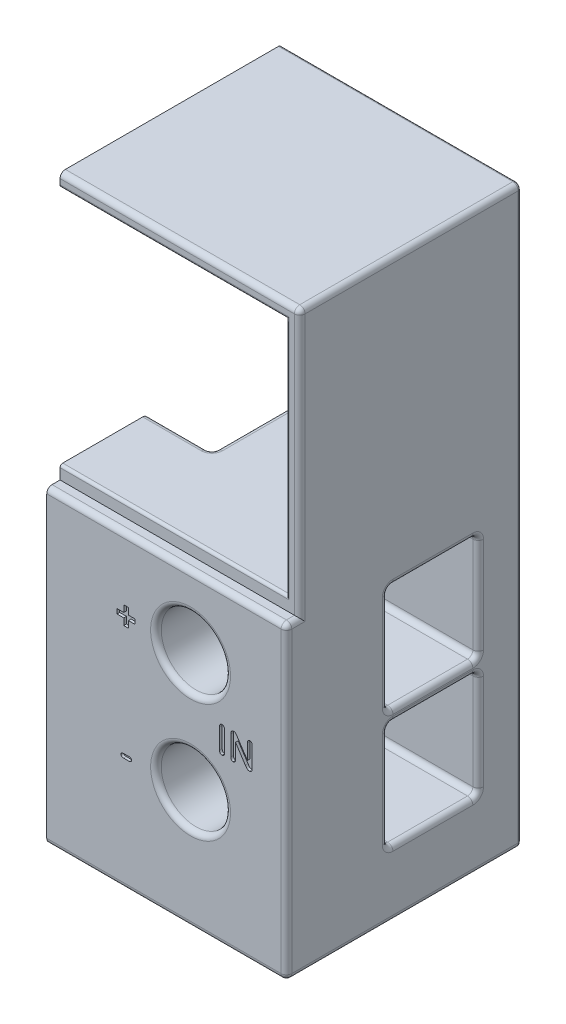
SolidWorks part; units mm, degrees
ref_plane "Front Plane" through (0, 0, 0) normal (0, 0, 1) x (1, 0, 0)
ref_plane "Top Plane" through (0, 0, 0) normal (0, 1, 0) x (1, 0, 0)
ref_plane "Right Plane" through (0, 0, 0) normal (1, 0, 0) x (0, 0, -1)
sketch "Sketch2" plane through (0, 0, 0) normal (0, 0, 1) x (1, 0, 0)
  line L0 (0, 32.5) -> (0, 0) construction
  line L1 (43.9999, -54) -> (-43.9999, -54)
  line L2 (43.9999, -54) -> (43.9999, 54)
  line L3 (43.9999, 54) -> (-43.9999, 54)
  line L4 (-43.9999, -54) -> (-43.9999, 54)
  line L5 (43.9999, -54) -> (-43.9999, 54) construction
  line L6 (43.9999, 54) -> (-43.9999, -54) construction
  line L9 (0, 0) -> (0, -20.5) construction
  line L10 (-31.75, 43.125) -> (31.75, 43.125)
  line L11 (-31.75, 43.125) -> (-31.75, 21.875)
  line L12 (-31.75, 21.875) -> (31.75, 21.875)
  line L13 (31.75, 43.125) -> (31.75, 21.875)
  line L14 (-31.75, 43.125) -> (31.75, 21.875) construction
  line L15 (-31.75, 21.875) -> (31.75, 43.125) construction
  line L16 (27, -31.625) -> (-27, -31.625)
  line L17 (27, -31.625) -> (27, -9.375)
  line L18 (27, -9.375) -> (-27, -9.375)
  line L19 (-27, -31.625) -> (-27, -9.375)
  line L20 (27, -31.625) -> (-27, -9.375) construction
  line L21 (27, -9.375) -> (-27, -31.625) construction
  circle A0 centre (-27, -9.375) radius 6.5
  circle A1 centre (27, -9.375) radius 6.5
  circle A2 centre (27, -31.625) radius 6.5
  circle A3 centre (-27, -31.625) radius 6.5
  point P0 (0, 0)
  point P5 (0, 32.5)
  point P26 (0, -20.5)
  dimension "D4" = 13
  dimension "D1" = 108
  dimension "D2" = 21.25
  dimension "D3" = 63.5
  dimension "D5" = 22.25
  dimension "D6" = 54
  dimension "D7" = 87.9997
  dimension "D8" = 32.5
  dimension "D9" = 20.5
extrude "Boss-Extrude1" add sketch "Sketch2" against normal blind 46 contours L4 L1 L2 L3 A3 L19 A0 L18 A1 L17 A2 L16 L10 L13 L12 L11 | A3 L16 A2 L17 A1 L18 A0 L19 region at (0, -1.6874, 0) region at (0, -20.5, 0)
sketch "Sketch3" plane through (0, 0, 0) normal (1, 0, 0) x (0, 0, -1)
  line L0 (46, -54) -> (0, -54) construction
  line L1 (46, 54) -> (0.0001, 54)
  line L2 (46, 54) -> (46, -54)
  line L3 (46, -54) -> (0.0001, -54)
  line L4 (0.0001, 54) -> (0.0001, -54)
  line L5 (46, 54) -> (0.0001, -54) construction
  line L6 (46, -54) -> (0.0001, 54) construction
  line L7 (46, -54) -> (46, 54) construction
  line L8 (23, -15.875) -> (23, -25.125) construction
  line L9 (30.5308, -2.875) -> (30.5308, -15.875) construction
  line L18 (34, 0.625) -> (34, -19.375)
  line L19 (34, -9.375) -> (27.5, -9.375) construction
  line L20 (36, -19.375) -> (34, -19.375)
  line L21 (36, 0.625) -> (36, -19.375)
  line L22 (36, 0.625) -> (34, 0.625)
  line L23 (34, -19.375) -> (34, 0.625)
  line L24 (19, 0.625) -> (34, 0.625)
  line L25 (19, -19.375) -> (19, 0.625)
  line L26 (19, -19.375) -> (34, -19.375)
  line L27 (46, -2.875) -> (0, -2.875) construction
  line L28 (0, -15.875) -> (46, -15.875) construction
  line L29 (46, -25.125) -> (0, -25.125) construction
  line L30 (0.0001, -20.5) -> (46, -20.5) construction
  line L31 (34, -31.625) -> (27.5, -31.625) construction
  line L32 (30.5308, -38.125) -> (30.5308, -25.125) construction
  line L33 (19, -21.625) -> (34, -21.625)
  line L34 (19, -21.625) -> (19, -41.625)
  line L35 (19, -41.625) -> (34, -41.625)
  line L36 (34, -21.625) -> (34, -41.625)
  line L37 (36, -41.625) -> (34, -41.625)
  line L38 (36, -41.625) -> (36, -21.625)
  line L39 (36, -21.625) -> (34, -21.625)
  line L40 (34, -41.625) -> (34, -21.625)
  arc A1 (34, -17.625) -> (34, -1.125) centre (35.9856, -9.375) cw
  arc A2 (34, -23.375) -> (34, -39.875) centre (35.9856, -31.625) ccw
  point P0 (23, 0)
  point P8 (30.5308, -9.375)
  point P19 (23, -20.5)
  point P48 (23, -41)
  dimension "D4" = 6.5
  dimension "D7" = 1.75
  dimension "D1" = 108
  dimension "D2" = 20
  dimension "D3" = 45.9999
  dimension "D5" = 2
  dimension "D6" = 15
  dimension "D8" = 10
sketch "Sketch4" plane through (0, 0, -46) normal (0, 0, -1) x (-1, 0, 0)
  line L1 (-31.75, 21.875) -> (31.75, 21.875)
  line L2 (-31.75, 21.875) -> (-31.75, 43.125)
  line L3 (-31.75, 43.125) -> (31.75, 43.125)
  line L4 (31.75, 21.875) -> (31.75, 43.125)
extrude "Boss-Extrude2" add sketch "Sketch4" against normal offset from surface (44 mm away) 2 up to face at (-20.5, -9.375, 0)
sketch "Sketch5" plane through (0, 0, -46) normal (0, 0, -1) x (-1, 0, 0)
  circle A0 centre (-27, -9.375) radius 6.5
  circle A1 centre (-27, -31.625) radius 6.5
  circle A2 centre (27, -31.625) radius 6.5
  circle A3 centre (27, -9.375) radius 6.5
  circle A5 centre (-27, -9.375) radius 6.5 construction
extrude "Boss-Extrude3" add sketch "Sketch5" against normal blind 10
sketch "Sketch7" plane through (0, 0, 0) normal (0, 0, 1) x (1, 0, 0)
  line L0 (-45, -54) -> (45, 54) construction
  line L1 (-45, 54) -> (45, 54)
  line L2 (-45, 54) -> (-45, -54)
  line L3 (-45, -54) -> (45, -54)
  line L4 (45, 54) -> (45, -54)
  line L5 (43.9999, 54) -> (-43.9999, 54) construction
  line L7 (-43.9999, 54) -> (43.9999, 54)
  line L8 (-43.9999, 54) -> (-43.9999, -54)
  line L9 (-43.9999, -54) -> (43.9999, -54)
  line L10 (43.9999, 54) -> (43.9999, -54)
  line M10 (-43.9999, 54) -> (-43.9999, -54)
  line M12 (43.9999, -54) -> (43.9999, 54)
  dimension "D1" = 90
extrude "Boss-Extrude4" add sketch "Sketch7" against normal up to surface (46 mm away) contours L0 L3 L4 M12 | L2 L0 L1 M10 | L10 L0 L1 | L0 L3 L8 region at (-44.5009, 0.2995, 0) region at (-44.3332, -53.5999, 0) region at (44.3332, 53.5999, 0) region at (44.5009, -0.2995, 0) up to face at (0, 0, -46)
extrude "Cut-Extrude1" cut sketch "Sketch3" along normal blind 28 from surface contours L18 A1 L24 L25 L26 | L21 L22 L18 L23 L20 | A2 L36 L33 L34 L35 | L40 A2 | L38 L39 L36 L40 L37 | A1 L23 region at (0, -9.375, -35) region at (0, -9.375, -24.7667) region at (0, -9.375, -31.2897) region at (0, -31.625, -24.7667) region at (0, -31.625, -35) region at (0, -31.625, -31.2897) starting at face at (-45, 0, -23)
extrude "Cut-Extrude2" cut sketch "Sketch3<3>" against normal blind 28 from surface contours L18 A1 L24 L25 L26 | A1 L23 | L21 L22 L18 L23 L20 | L38 L39 L36 L40 L37 | L40 A2 | A2 L36 L33 L34 L35 region at (0, -9.375, -35) region at (0, -9.375, -24.7667) region at (0, -9.375, -31.2897) region at (0, -31.625, -24.7667) region at (0, -31.625, -35) region at (0, -31.625, -31.2897) starting at face at (45, 0, -23)
sketch "Sketch3<3>" plane through (0, 0, 0) normal (1, 0, 0) x (0, 0, -1) same geometry as "Sketch3"
sketch "Sketch6" plane through (0, 0, 0) normal (0, 0, 1) x (1, 0, 0)
  line L1 (-42.5, 51.5) -> (42.5, 51.5)
  line L2 (-42.5, 51.5) -> (-42.5, 6.5)
  line L3 (-42.5, 6.5) -> (42.5, 6.5)
  line L4 (42.5, 51.5) -> (42.5, 6.5)
  line L5 (-42.5, 51.5) -> (42.5, 6.5) construction
  line L6 (-45, 54) -> (45, 54)
  line L7 (-45, 54) -> (-45, 4)
  line L8 (-45, 4) -> (45, 4)
  line L9 (45, 54) -> (45, 4)
  line L10 (45, 54) -> (-45, 4) construction
  point P9 (0, 29)
  line M13 (-31.75, 43.125) -> (31.75, 43.125)
  line M14 (31.75, 43.125) -> (31.75, 21.875)
  line M15 (31.75, 21.875) -> (-31.75, 21.875)
  line M16 (-31.75, 21.875) -> (-31.75, 43.125)
  dimension "D1" = 85
  dimension "D2" = 45
  dimension "D3" = 90
  dimension "D4" = 50
extrude "Cut-Extrude4" cut sketch "Sketch6" against normal through all contours L4 L1 L2 L3 M16 M13 M14 M15 | M13 M16 M15 M14 region at (0, 50.5382, 0) region at (0, 32.5, 0)
sketch "Sketch8" plane through (0, 0, -36) normal (0, 0, 1) x (1, 0, 0)
  circle A0 centre (-27, -9.375) radius 4.25
  circle A1 centre (-27, -31.625) radius 4.25
  circle A2 centre (27, -31.625) radius 4.25
  circle A3 centre (27, -9.375) radius 4.25
  circle A4 centre (27, -31.625) radius 6.5 construction
  circle A5 centre (27, -9.375) radius 6.5 construction
  circle A6 centre (-27, -9.375) radius 6.5 construction
  circle A7 centre (-27, -31.625) radius 6.5 construction
  dimension "D1" = 8.5
extrude "Cut-Extrude5" cut sketch "Sketch8" against normal through all
sketch "Sketch9" plane through (0, 0, -46) normal (0, 0, -1) x (-1, 0, 0)
  line L0 (0, -51.5) -> (0, -54) construction
  line L1 (-42.5, 51.5) -> (42.5, 51.5)
  line L2 (-42.5, 51.5) -> (-42.5, -51.5)
  line L3 (-42.5, -51.5) -> (42.5, -51.5)
  line L4 (42.5, 51.5) -> (42.5, -51.5)
  line L5 (-45, -54) -> (45, -54) construction
  line L6 (42.5, 0) -> (45, 0) construction
  line L7 (45, -54) -> (45, 54) construction
extrude "Cut-Extrude6" cut sketch "Sketch9" against normal blind 8
extrude "Cut-Extrude7" cut sketch "Sketch6<4>" against normal blind 2.5
sketch "Sketch6<4>" plane through (0, 0, 0) normal (0, 0, 1) x (1, 0, 0) same geometry as "Sketch6"
sketch "Sketch10" plane through (0, 0, 0) normal (1, 0, 0) x (0, 0, -1)
  line L0 (46, -54) -> (0, -54) construction
  line L1 (46, 54) -> (44, 54)
  line L2 (46, 54) -> (46, -54)
  line L3 (46, -54) -> (44, -54)
  line L4 (44, 54) -> (44, -54)
  dimension "D1" = 2
extrude "Cut-Extrude8" cut sketch "Sketch10" against normal through all both and the other way through all
fillet "Fillet2" radius 1 74 edges at (-45, -41.625, -27.5) (-45, -21.625, -27.5) (-45, -19.375, -27.5) (-45, 0.625, -27.5) (-17, -19.375, -27.5) (-17, 0.625, -27.5) (-31, -21.625, -36) (-31, -41.625, -36) (-45, -31.625, -36) (-22.75, -31.625, -36) (-31, 0.625, -36) (-17, -9.375, -36) (-31, -19.375, -36) (-45, -9.375, -36) (-22.75, -9.375, -36) (-17, -41.625, -27.5) (-17, -31.625, -36) (-17, -21.625, -27.5) (-27, -38.125, -19) (-31, -41.625, -19) (-17, -31.625, -19) (-31, -21.625, -19) (-45, -31.625, -19) (-27, -2.875, -19) (-31, -19.375, -19) (-17, -9.375, -19) (-31, 0.625, -19) (-45, -9.375, -19) (45, -19.375, -27.5) (27, -2.875, -19) (31, -19.375, -19) (45, -9.375, -19) (17, -19.375, -27.5) (17, -9.375, -19) (17, 0.625, -27.5) (31, 0.625, -19) (45, 0.625, -27.5) (31, -19.375, -36) (17, -9.375, -36) (31, 0.625, -36) (45, -9.375, -36) (31.25, -9.375, -36) (45, -41.625, -27.5) (31, -41.625, -36) (45, -31.625, -36) (31.25, -31.625, -36) (31, -21.625, -36) (45, -21.625, -27.5) (27, -38.125, -19) (31, -21.625, -19) (31, -41.625, -19) (45, -31.625, -19) (17, -31.625, -19) (17, -21.625, -27.5) (17, -31.625, -36) (17, -41.625, -27.5) (0, 6.5, -38) (45, -54, -22) (-45, -54, -22) (-45, 54, -23.25) (-45, 4, -1.25) (-45, 29, -2.5) (-45, -25, 0) (0, -54, 0) (0, 4, 0) (45, 4, -1.25) (45, -25, 0) (45, 54, -23.25) (45, 29, -2.5) (0, 54, -2.5) (-20.5, -31.625, 0) (33.5, -9.375, 0) (33.5, -31.625, 0) (-20.5, -9.375, 0)
fillet "Fillet3" radius 0.5 20 edges at (44.7071, 53.7071, -44) (0, 54, -44) (-44.7071, 53.7071, -44) (-45, 0, -44) (-44.7071, -53.7071, -44) (0, -54, -44) (44.7071, -53.7071, -44) (45, 0, -44) (42.5, 0, -44) (0, -51.5, -44) (-42.5, 0, -44) (0, 51.5, -44) (-31.25, -31.625, -38) (22.75, -9.375, -38) (22.75, -31.625, -38) (-31.25, -9.375, -38) (-42.5, 29, -2.5) (0, 6.5, -2.5) (42.5, 29, -2.5) (0, 51.5, -2.5)
sketch "Sketch11" plane through (0, 0, -38) normal (0, 0, -1) x (-1, 0, 0)
  line L0 (-42.5, 6.5) -> (42.5, 6.5) construction
  line L1 (-12, 6.5) -> (12, 6.5)
  line L2 (-12, 6.5) -> (-12, -51.5)
  line L3 (-12, -51.5) -> (12, -51.5)
  line L4 (12, 6.5) -> (12, -51.5)
  line L5 (-12, 6.5) -> (12, -51.5) construction
  line L6 (-12, -51.5) -> (12, 6.5) construction
  line L7 (-42.5, -51.5) -> (42.5, -51.5) construction
  line L8 (0, -22.5) -> (0, 0) construction
  line L9 (-17, -0.375) -> (-17, -18.375) construction
  point P0 (0, -22.5)
  dimension "D1" = 5
extrude "Cut-Extrude9" cut sketch "Sketch11" against normal up to surface (19 mm away) up to face at (-27, -1.875, -19)
fillet "Fillet4" radius 1 10 edges at (12, -23, -38) (-12, -23, -38) (12, 6.2071, -37.7071) (-12, 6.2071, -37.7071) (12, 6.5, -28) (-12, 6.5, -28) (0, -51.5, -19) (12, -22.5, -19) (0, 6.5, -19) (-12, -22.5, -19)
sketch "Sketch12" plane through (0, 0, 0) normal (0, 0, 1) x (1, 0, 0)
  line L0 (-27, -9.375) -> (-27, -31.625) construction
  line L1 (-19.5, -9.375) -> (-19.5, -31.625) construction
  line L4 (-19.5, -20.5) -> (-44, -20.5) construction
  line L5 (-44, 3) -> (-44, -53) construction
  line L6 (-27, -9.375) -> (-19.5, -9.375) construction
  line L7 (-44, -23) -> (-27, -23) construction
  line L8 (27, -9.375) -> (27, -31.625) construction
  line L9 (-19.9289, -11.875) -> (-9.9289, -11.875) construction
  line L11 (-19.5, -9.375) -> (27, -9.375) construction
  line L12 (-19.5, -31.625) -> (27, -31.625) construction
  line L13 (-9.9289, -11.875) -> (9.9289, -11.875) construction
  line L14 (-19.9289, -34.125) -> (-9.9289, -34.125) construction
  line L15 (-19.9289, -11.875) -> (-19.9289, -34.125) construction
  line L16 (-27, -23) -> (27, -23) construction
  line L17 (27, -23) -> (44, -23) construction
  line L18 (44, -53) -> (44, 3) construction
  line L19 (9.9289, -11.875) -> (19.9289, -11.875) construction
  line L20 (19.9289, -11.875) -> (19.9289, -34.125) construction
  line L21 (-9.9289, -34.125) -> (9.9289, -34.125) construction
  line L22 (9.9289, -34.125) -> (19.9289, -34.125) construction
  line L23 (0, -11.875) -> (0, -34.125) construction
  circle A0 centre (-27, -9.375) radius 7.5 construction
  circle A1 centre (-27, -31.625) radius 7.5 construction
  circle A2 centre (27, -31.625) radius 7.5 construction
  circle A4 centre (27, -9.375) radius 7.5 construction
  text T0 "OUT" font "Arial Rounded MT Bold" height 5
  text T1 "IN" font "Arial Rounded MT Bold" height 5
  text T2 "+" font "Arial Rounded MT Bold" height 5
  text T3 "-" font "Arial Rounded MT Bold" height 5
  text T4 "+" font "Arial Rounded MT Bold" height 5
  text T5 "-" font "Arial Rounded MT Bold" height 5
  point P10 (-27, -20.5)
  dimension "D1" = 2.5
  dimension "D2" = 2.5
  dimension "D3" = 10
  dimension "D4" = 10
extrude "Cut-Extrude10" cut sketch "Sketch12" against normal blind 0.5
sketch "Sketch13" plane through (0, 0, 0) normal (0, 0, 1) x (1, 0, 0)
  line L0 (44, -54) -> (-44, -54) construction
  line L1 (-45, 54) -> (0, 54)
  line L2 (-45, 54) -> (-45, -54)
  line L3 (-45, -54) -> (0, -54)
  line L4 (0, 54) -> (0, -54)
  line L5 (45, 3) -> (45, -53) construction
  line L6 (0, 54) -> (45, 54)
  line L7 (0, 54) -> (0, -54)
  line L8 (0, -54) -> (45, -54)
  line L9 (45, 54) -> (45, -54)
  line L10 (-45, -53) -> (-45, 3) construction
  line L11 (-44, 54) -> (44, 54) construction
extrude "Cut-Extrude12" cut sketch "Sketch13" against normal through all contours L4 L1 L2 L3 region at (-22.5, 0, 0)
